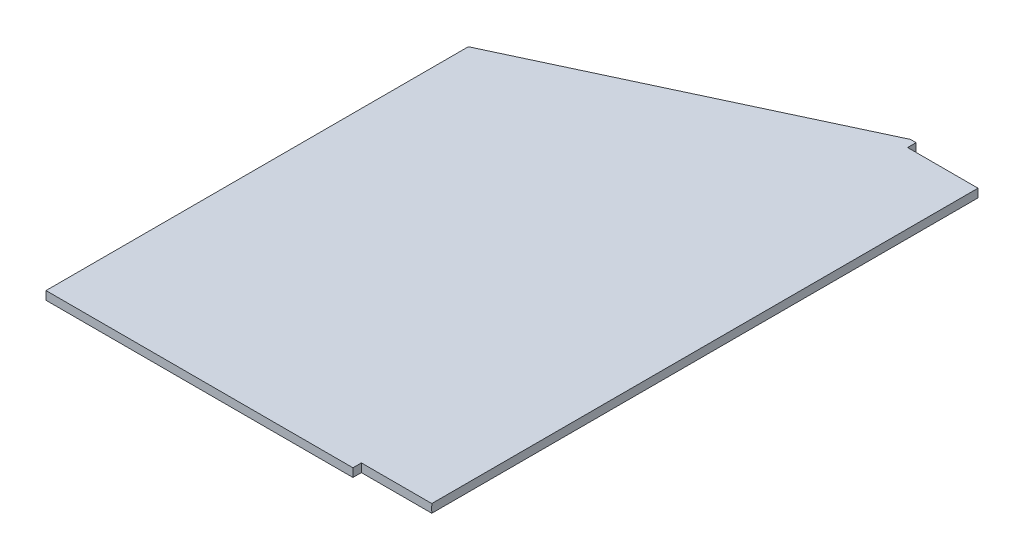
SolidWorks part; units mm, degrees
ref_plane "Front Plane" through (0, 0, 0) normal (0, 0, 1) x (1, 0, 0)
ref_plane "Top Plane" through (0, 0, 0) normal (0, 1, 0) x (1, 0, 0)
ref_plane "Right Plane" through (0, 0, 0) normal (1, 0, 0) x (0, 0, -1)
sketch "Sketch1" plane through (0, 0, 0) normal (0, 1, 0) x (1, 0, 0)
  line L0 (-107, 150) -> (-107, 0)
  line L1 (-107, 0) -> (0, 0)
  line L2 (0, 0) -> (0, 200) construction
  line L3 (0, 200) -> (-107, 150)
  line L15 (0, 0) -> (78.2, 0)
  line L17 (0, 200) -> (78.2, 200)
  line L18 (78.2, 0) -> (78.2, 200)
  dimension "D1" = 200
  dimension "D2" = 150
  dimension "D3" = 107
  dimension "D4" = 78.2
extrude "Boss-Extrude1" add sketch "Sketch1" along normal blind 1.5 and the other way blind 1.5
sketch "Sketch2" plane through (0, 0, -200) normal (0, 0, -1) x (-1, 0, 0)
  line L0 (-78.2, -1.5) -> (-78.2, 1.5) construction
  circle A0 centre (-78.2, 0) radius 51.2
  dimension "D1" = 102.4
extrude "Cut-Extrude1" cut sketch "Sketch2" against normal through all
sketch "Sketch3" plane through (0, 0, -200) normal (0, 0, -1) x (-1, 0, 0)
  line L0 (0, 0) -> (-78.2, 0) construction
  circle A0 centre (-78.2, 0) radius 76.2
  dimension "D2" = 152.4
  dimension "D1" = 78.2
extrude "Cut-Extrude2" cut sketch "Sketch3" against normal blind 3
sketch "Sketch4" plane through (0, 0, 0) normal (0, 0, 1) x (1, 0, 0)
  line L0 (0, 0) -> (78.2, 0) construction
  circle A0 centre (78.2, 0) radius 76.2
  dimension "D2" = 152.4
  dimension "D1" = 78.2
extrude "Cut-Extrude3" cut sketch "Sketch4" against normal blind 3
